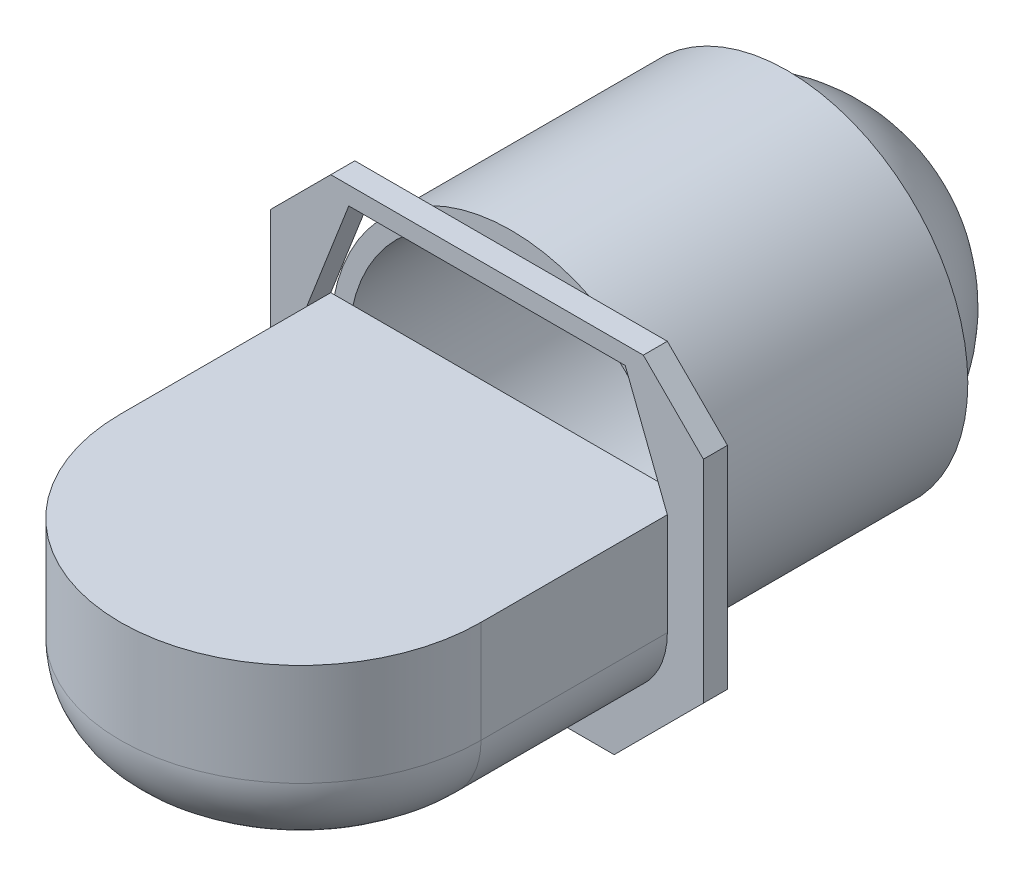
SolidWorks part; units mm, degrees
ref_plane "Спереди" through (0, 0, 0) normal (0, 0, 1) x (1, 0, 0)
ref_plane "Сверху" through (0, 0, 0) normal (0, 1, 0) x (1, 0, 0)
ref_plane "Справа" through (0, 0, 0) normal (1, 0, 0) x (0, 0, -1)
other "Configuration Table"
sketch "Sketch1" plane through (0, 0, 0) normal (0, 0, 1) x (1, 0, 0)
  circle A0 centre (0, 0) radius 30
  circle A1 centre (0, 0) radius 27
  dimension "D1" = 60
  dimension "D2" = 3
extrude "Boss-Extrude1" add sketch "Sketch1" along normal blind 46
sketch "Sketch3" plane through (0, 0, 0) normal (0, 1, 0) x (1, 0, 0)
  line L1 (27, 0) -> (0, 0)
  line L2 (0, 0) -> (0, 20)
  line L3 (0, 24.3239) -> (0, -4.1272) construction
  arc A0 (0, 20) -> (27, 0) centre (0, -8.225) cw
  dimension "D1" = 20
revolve "Revolve1" add sketch "Sketch3" angle 360 about L3 other way angle 360
sketch "Sketch5" plane through (0, 0, 0) normal (0, 1, 0) x (1, 0, 0)
  line L0 (0, 31.462) -> (0, -103.4558) construction
  line L1 (-30, -46) -> (-30, -81)
  line L2 (-30, -46) -> (30, -46) construction
  line L3 (30, -81) -> (30, -46)
  line L4 (30, -46) -> (-30, -46)
  arc A0 (-30, -81) -> (30, -81) centre (0, -81) ccw
  dimension "D1" = 60
  dimension "D2" = 35
extrude "Boss-Extrude2" add sketch "Sketch5" along normal blind 6 and the other way blind 24 separate body
fillet "Fillet1" radius 13 3 edges at (30, -24, 63.5) (0, -24, 111) (-30, -24, 63.5)
sketch "Sketch7" plane through (0, 0, 46) normal (0, 0, 1) x (1, 0, 0)
  line L0 (-36, 17) -> (-36, -18.1508)
  line L1 (-36, -18.1508) -> (-21.1508, -33)
  line L2 (-21.1508, -33) -> (21.1508, -33)
  line L3 (21.1508, -33) -> (36, -18.1508)
  line L4 (36, -18.1508) -> (36, 17)
  line L5 (36, 17) -> (26, 27)
  line L6 (26, 27) -> (-26, 27)
  line L7 (-26, 27) -> (-36, 17)
  line L8 (0, 40.4452) -> (0, -48.0985) construction
  line L9 (-30, 6) -> (30, 6)
  line L10 (30, 6) -> (23, 24)
  line L11 (23, 24) -> (-23, 24)
  line L12 (-23, 24) -> (-30, 6)
  circle A0 centre (0, 0) radius 27 construction
  point P15 (-30, 6)
  point P18 (-34.0792, 16.0132)
  point P21 (36, -21.4299)
  dimension "D1" = 6
  dimension "D2" = 18
  dimension "D3" = 46
  dimension "D4" = 52
  dimension "D5" = 60
  dimension "D6" = 45
  dimension "D7" = 21
extrude "Boss-Extrude7" add sketch "Sketch7" along normal blind 4
